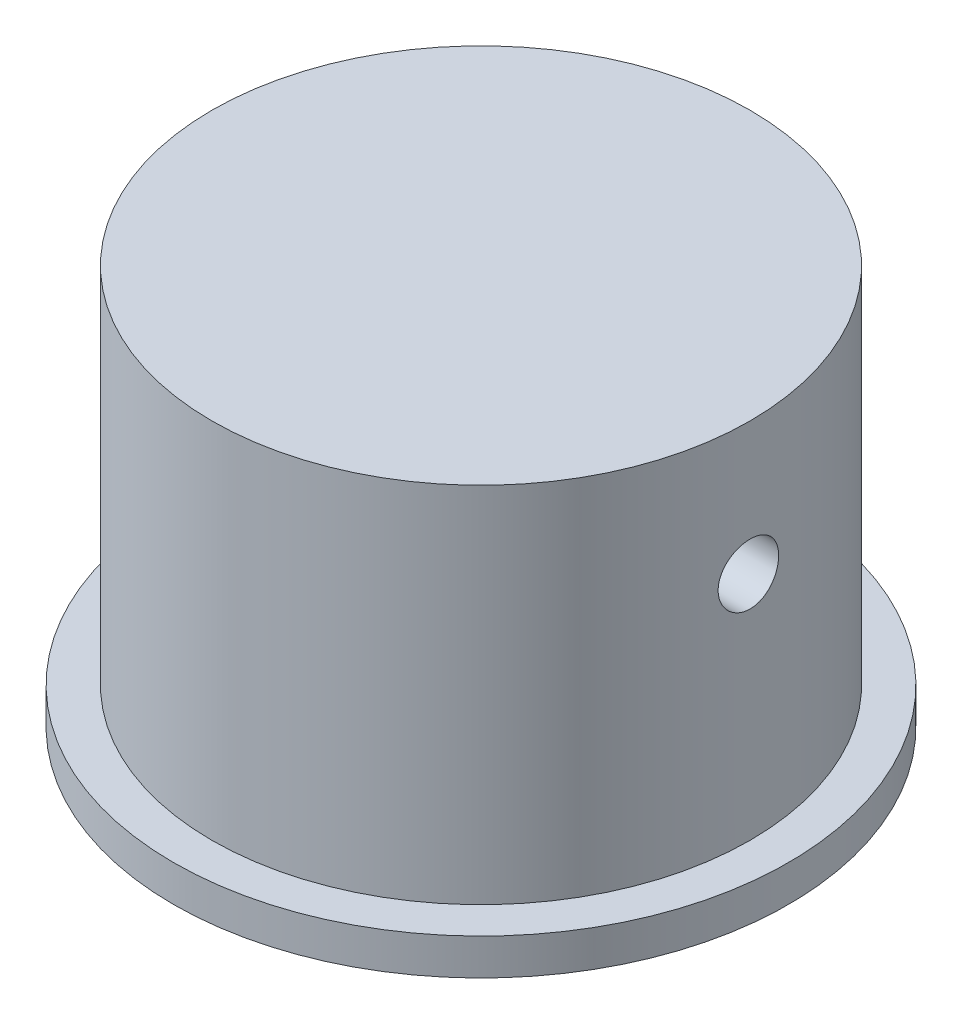
SolidWorks part; units mm, degrees
material "ABS"
ref_plane "Front Plane" through (0, 0, 0) normal (0, 0, 1) x (1, 0, 0)
ref_plane "Top Plane" through (0, 0, 0) normal (0, 1, 0) x (1, 0, 0)
ref_plane "Right Plane" through (0, 0, 0) normal (1, 0, 0) x (0, 0, -1)
sketch "Sketch1" plane through (0, 0, 0) normal (1, 0, 0) x (0, 0, -1)
  line L3 (-12.7, 0) -> (-12.7, 1.5)
  line L4 (-12.7, 1.5) -> (-11.1125, 1.5)
  line L5 (-11.1125, 1.5) -> (-11.1125, 16.5)
  line L6 (-11.1125, 16.5) -> (0, 16.5)
  line L9 (0, 16.5) -> (0, 5)
  line L10 (0, -1000) -> (0, 49000) construction
  line L11 (-12.7, 0) -> (-2.8067, 0)
  line L12 (-2.8067, 0) -> (-2.8067, 5)
  line L13 (-2.8067, 5) -> (0, 5)
  dimension "D1" = 12.7
  dimension "D2" = 11.1125
  dimension "D3" = 5
  dimension "D4" = 15
  dimension "D5" = 0
  dimension "D6" = 2.8067
  dimension "D7" = 1.5
revolve "Revolve1" add sketch "Sketch1" angle 360 about L10
ref_plane "Plane1" through (11.1125, 0, 0) normal (1, 0, 0) x (0, 0, -1)
hole_wizard "M3x0.5 Tapped Hole1" positions "Sketch2" profile "Sketch4" tap size "M3x0.5" standard "ANSI Metric"
sketch "Sketch2" plane through (11.1125, 0, 0) normal (1, 0, 0) x (0, 0, -1)
  line L0 (12.7, 1.5) -> (-12.7, 1.5) construction
  point P0 (0, 11.025)
  point P2 (0, 0)
  dimension "D1" = 9.525
sketch "Sketch4" plane through (11.1125, 11.025, 0) normal (0, 1, 0) x (0, 0, -1)
  line L0 (0, 0) -> (0, 10.7511)
  line L1 (0, 10.7511) -> (1.25, 10)
  line L2 (1.25, 10) -> (1.25, 0)
  line L5 (1.25, 0) -> (0, 0)
  line L10 (0, 10.7511) -> (-1.25, 10) construction
  line L11 (0, -6.35) -> (0, 107.95) construction
  dimension "Tap Drill Dia." = 2.5
  dimension "Tap Drill Depth" = 10
  dimension "Drill Angle" = 118
cosmetic thread "Hole Thread1" parameters "D1"=6, "D2"=3
mirror "Mirror1" about plane through (0, 0, 0) normal (1, 0, 0) of "M3x0.5 Tapped Hole1"
cosmetic thread "Hole Thread2"
